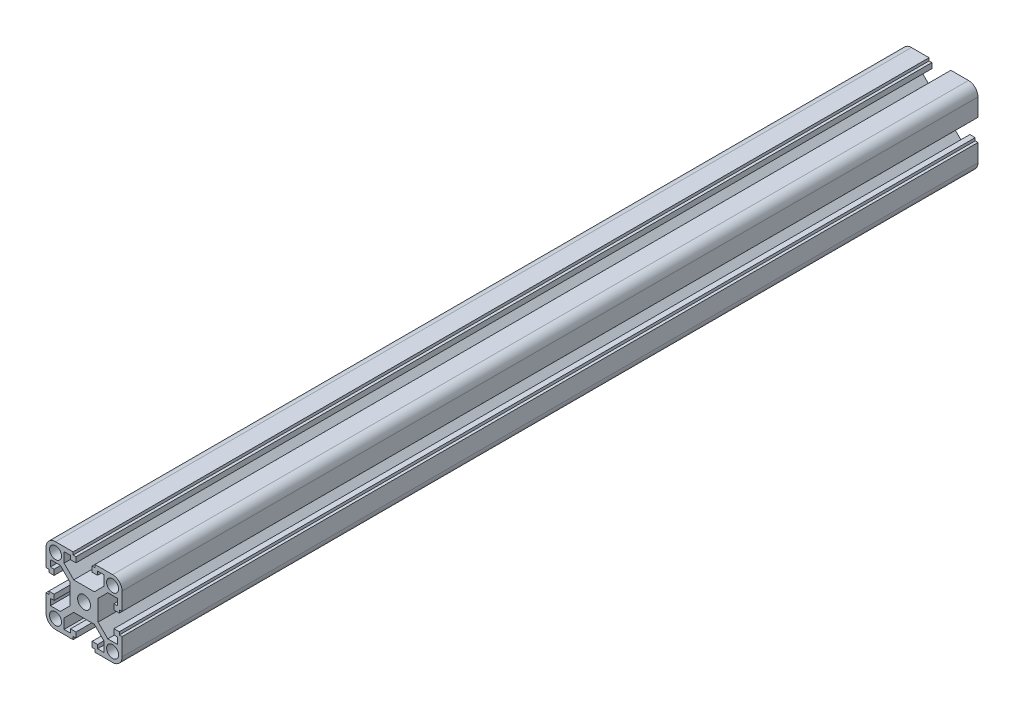
SolidWorks part; units mm, degrees
material "АД1 ГОСТ 4784-97"
ref_plane "Спереди" through (0, 0, 0) normal (0, 0, 1) x (1, 0, 0)
ref_plane "Сверху" through (0, 0, 0) normal (0, 1, 0) x (1, 0, 0)
ref_plane "Справа" through (0, 0, 0) normal (1, 0, 0) x (0, 0, -1)
ref_axis "ОсьX" through (-88.99, 0, 0) along (1, 0, 0)
ref_axis "ОсьZ" through (0, 55, 0) along (0, -1, 0)
ref_axis "ОсьY" through (0, 0, -88.99) along (0, 0, 1)
sketch "Эскиз1" plane through (0, 0, 0) normal (0, 0, 1) x (1, 0, 0)
  line L0 (-15, 20) -> (-5.7274, 20)
  line L1 (-5.7274, 20) -> (-5.7274, 18.5304)
  line L2 (-5.7274, 18.5304) -> (-4.25, 18.5304)
  line L3 (-4.25, 18.5304) -> (-4.25, 15.732)
  line L4 (-4.25, 15.732) -> (-7.1118, 15.732)
  line L5 (-7.1118, 15.732) -> (-7.1118, 17.7)
  line L6 (-7.1118, 17.7) -> (-10.5, 17.7)
  line L7 (-10.5, 17.7) -> (-10.5, 12.4799)
  line L8 (-10.5, 12.4799) -> (-5.4201, 7.4)
  line L9 (-20, 15) -> (-20, 5.7274)
  line L10 (0, 0) -> (0, 8.4096) construction
  line L11 (-15, 15) -> (0, 0) construction
  line L12 (10.5, 12.4799) -> (5.4201, 7.4)
  line L13 (10.5, 17.7) -> (10.5, 12.4799)
  line L14 (7.1118, 17.7) -> (10.5, 17.7)
  line L15 (7.1118, 15.732) -> (7.1118, 17.7)
  line L16 (4.25, 15.732) -> (7.1118, 15.732)
  line L17 (4.25, 18.5304) -> (4.25, 15.732)
  line L18 (5.7274, 18.5304) -> (4.25, 18.5304)
  line L19 (5.7274, 20) -> (5.7274, 18.5304)
  line L20 (15, 20) -> (5.7274, 20)
  line L21 (-5.4201, 7.4) -> (5.4201, 7.4)
  line L22 (-8.8445, 0) -> (0, 0) construction
  line L23 (-12.4799, 10.5) -> (-7.4, 5.4201)
  line L24 (-17.7, 10.5) -> (-12.4799, 10.5)
  line L25 (-17.7, 7.1118) -> (-17.7, 10.5)
  line L26 (-15.732, 7.1118) -> (-17.7, 7.1118)
  line L27 (-15.732, 4.25) -> (-15.732, 7.1118)
  line L28 (-18.5304, 4.25) -> (-15.732, 4.25)
  line L29 (-18.5304, 5.7274) -> (-18.5304, 4.25)
  line L30 (-20, 5.7274) -> (-18.5304, 5.7274)
  line L31 (18.5304, 5.7274) -> (18.5304, 4.25)
  line L32 (18.5304, 4.25) -> (15.732, 4.25)
  line L33 (15.732, 4.25) -> (15.732, 7.1118)
  line L34 (15.732, 7.1118) -> (17.7, 7.1118)
  line L35 (12.4799, 10.5) -> (7.4, 5.4201)
  line L36 (17.7, 10.5) -> (12.4799, 10.5)
  line L37 (17.7, 7.1118) -> (17.7, 10.5)
  line L38 (20, 5.7274) -> (18.5304, 5.7274)
  line L39 (20, 15) -> (20, 5.7274)
  line L40 (20, -15) -> (20, -5.7274)
  line L41 (20, -5.7274) -> (18.5304, -5.7274)
  line L42 (17.7, -7.1118) -> (17.7, -10.5)
  line L43 (17.7, -10.5) -> (12.4799, -10.5)
  line L44 (12.4799, -10.5) -> (7.4, -5.4201)
  line L45 (15.732, -7.1118) -> (17.7, -7.1118)
  line L46 (15.732, -4.25) -> (15.732, -7.1118)
  line L47 (18.5304, -4.25) -> (15.732, -4.25)
  line L48 (18.5304, -5.7274) -> (18.5304, -4.25)
  line L49 (-20, -5.7274) -> (-18.5304, -5.7274)
  line L50 (-18.5304, -5.7274) -> (-18.5304, -4.25)
  line L51 (-18.5304, -4.25) -> (-15.732, -4.25)
  line L52 (-15.732, -4.25) -> (-15.732, -7.1118)
  line L53 (-15.732, -7.1118) -> (-17.7, -7.1118)
  line L54 (-17.7, -7.1118) -> (-17.7, -10.5)
  line L55 (-17.7, -10.5) -> (-12.4799, -10.5)
  line L56 (-12.4799, -10.5) -> (-7.4, -5.4201)
  line L57 (-5.4201, -7.4) -> (5.4201, -7.4)
  line L58 (15, -20) -> (5.7274, -20)
  line L59 (5.7274, -20) -> (5.7274, -18.5304)
  line L60 (5.7274, -18.5304) -> (4.25, -18.5304)
  line L61 (4.25, -18.5304) -> (4.25, -15.732)
  line L62 (4.25, -15.732) -> (7.1118, -15.732)
  line L63 (7.1118, -15.732) -> (7.1118, -17.7)
  line L64 (7.1118, -17.7) -> (10.5, -17.7)
  line L65 (10.5, -17.7) -> (10.5, -12.4799)
  line L66 (10.5, -12.4799) -> (5.4201, -7.4)
  line L67 (-20, -15) -> (-20, -5.7274)
  line L68 (-10.5, -12.4799) -> (-5.4201, -7.4)
  line L69 (-10.5, -17.7) -> (-10.5, -12.4799)
  line L70 (-7.1118, -17.7) -> (-10.5, -17.7)
  line L71 (-7.1118, -15.732) -> (-7.1118, -17.7)
  line L72 (-4.25, -15.732) -> (-7.1118, -15.732)
  line L73 (-4.25, -18.5304) -> (-4.25, -15.732)
  line L74 (-5.7274, -18.5304) -> (-4.25, -18.5304)
  line L75 (-5.7274, -20) -> (-5.7274, -18.5304)
  line L76 (-15, -20) -> (-5.7274, -20)
  line L77 (-7.4, 5.4201) -> (-7.4, -5.4201)
  line L78 (7.4, 5.4201) -> (7.4, -5.4201)
  circle A0 centre (0, 0) radius 3.4
  circle A1 centre (-15, 15) radius 3.15
  arc A2 (-15, 20) -> (-20, 15) centre (-15, 15) ccw
  arc A3 (15, 20) -> (20, 15) centre (15, 15) cw
  circle A4 centre (15, 15) radius 3.15
  circle A5 centre (15, -15) radius 3.15
  arc A6 (15, -20) -> (20, -15) centre (15, -15) ccw
  arc A7 (-15, -20) -> (-20, -15) centre (-15, -15) cw
  circle A8 centre (-15, -15) radius 3.15
  dimension "D1" = 6.8
  dimension "D2" = 6.3
  dimension "D3" = 40
  dimension "D8" = 30
  dimension "D4" = 2.3
  dimension "D5" = 1.35
  dimension "D6" = 21
  dimension "D7" = 8.5
  dimension "D9" = 45
  dimension "D10" = 2.8
  dimension "D11" = 4
  dimension "D13" = 40
extrude "Бобышка-Вытянуть1" add sketch "Эскиз1" along normal mid plane 450
